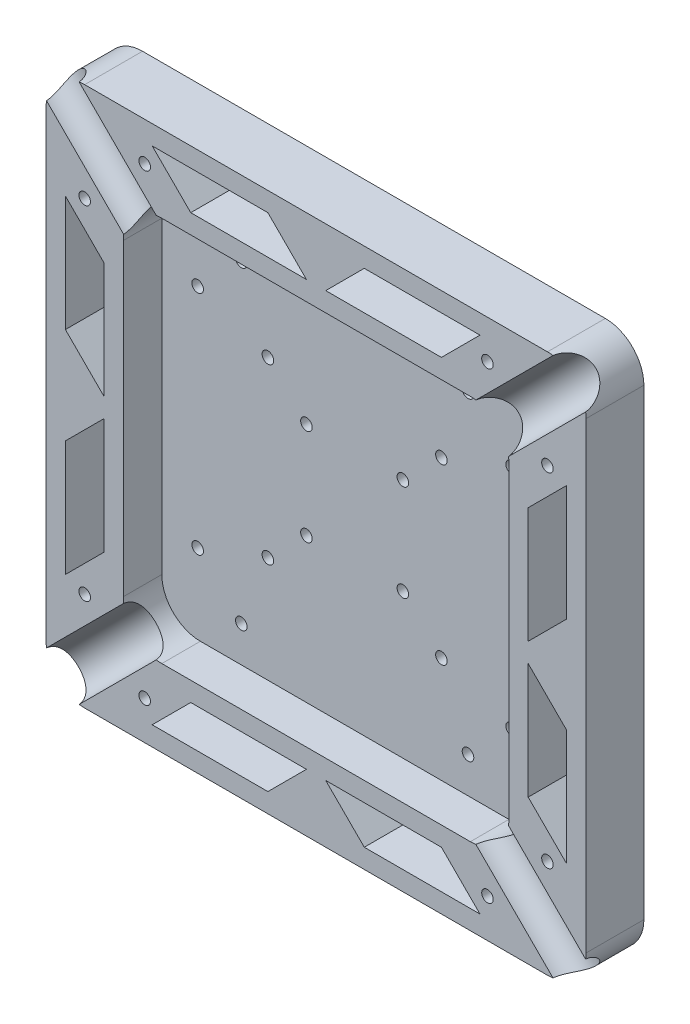
SolidWorks part; units mm, degrees
ref_plane "Plan de face" through (0, 0, 0) normal (0, 0, 1) x (1, 0, 0)
ref_plane "Plan de dessus" through (0, 0, 0) normal (0, 1, 0) x (1, 0, 0)
ref_plane "Plan de droite" through (0, 0, 0) normal (1, 0, 0) x (0, 0, -1)
sketch "Esquisse1" plane through (0, 0, 0) normal (0, 0, 1) x (1, 0, 0)
  line L0 (55, 75.9996) -> (55, -81.4607) construction
  line L1 (-70, 70) -> (70, 70)
  line L2 (-70, 70) -> (-70, -70)
  line L3 (-70, -70) -> (70, -70)
  line L4 (70, 70) -> (70, -70)
  line L9 (65, 75.9996) -> (65, -81.4607) construction
  line L10 (50, 0) -> (70, 0) construction
  line L11 (52.5, 0) -> (65, 12.5) construction
  line L12 (65, 12.5) -> (55, 2.5)
  line L13 (65, -12.5) -> (52.5, 0) construction
  line L14 (65, -12.5) -> (55, -2.5)
  line L15 (65, -12.5) -> (65, -42.5)
  line L16 (65, -42.5) -> (55, -32.5)
  line L17 (55, -32.5) -> (55, -2.5)
  line L18 (65, 12.5) -> (65, 42.5)
  line L19 (65, 42.5) -> (55, 32.5)
  line L20 (55, 32.5) -> (55, 2.5)
  line L21 (12.5, -65) -> (2.5, -55)
  line L22 (-12.5, -65) -> (-2.5, -55)
  line L23 (-12.5, -65) -> (-42.5, -65)
  line L24 (-42.5, -65) -> (-32.5, -55)
  line L25 (-32.5, -55) -> (-2.5, -55)
  line L26 (12.5, -65) -> (42.5, -65)
  line L27 (42.5, -65) -> (32.5, -55)
  line L28 (32.5, -55) -> (2.5, -55)
  line L29 (0, -52.5) -> (12.5, -65) construction
  line L30 (-12.5, -65) -> (0, -52.5) construction
  line L31 (-65, -12.5) -> (-55, -2.5)
  line L32 (-65, 12.5) -> (-55, 2.5)
  line L33 (-65, 12.5) -> (-65, 42.5)
  line L34 (-65, 42.5) -> (-55, 32.5)
  line L35 (-55, 32.5) -> (-55, 2.5)
  line L36 (-65, -12.5) -> (-65, -42.5)
  line L37 (-65, -42.5) -> (-55, -32.5)
  line L38 (-55, -32.5) -> (-55, -2.5)
  line L39 (-52.5, 0) -> (-65, -12.5) construction
  line L40 (-65, 12.5) -> (-52.5, 0) construction
  line L41 (-12.5, 65) -> (-2.5, 55)
  line L42 (12.5, 65) -> (2.5, 55)
  line L43 (12.5, 65) -> (42.5, 65)
  line L44 (42.5, 65) -> (32.5, 55)
  line L45 (32.5, 55) -> (2.5, 55)
  line L46 (-12.5, 65) -> (-42.5, 65)
  line L47 (-42.5, 65) -> (-32.5, 55)
  line L48 (-32.5, 55) -> (-2.5, 55)
  line L49 (0, 52.5) -> (-12.5, 65) construction
  line L50 (12.5, 65) -> (0, 52.5) construction
  dimension "D1" = 140
  dimension "D2" = 140
  dimension "D3" = 70
  dimension "D4" = 70
  dimension "D10" = 5
  dimension "D11" = 2.5
  dimension "D12" = 12.5
  dimension "D13" = 30
  dimension "D14" = 30
  dimension "D15" = 30
  dimension "D16" = 30
  dimension "D17" = 4
extrude "Boss.-Extru.1" add sketch "Esquisse1" along normal blind 15
ref_plane "Plan1" through (0, 0, 0) normal (-0.7071, 0.7071, 0) x (-0.7071, -0.7071, 0)
sketch "Esquisse4" plane through (0, 0, 15) normal (0, 0, 1) x (1, 0, 0)
  line L1 (-50, 50) -> (50, 50)
  line L2 (-50, 50) -> (-50, -50)
  line L3 (-50, -50) -> (50, -50)
  line L4 (50, 50) -> (50, -50)
  dimension "D1" = 100
  dimension "D2" = 100
  dimension "D3" = 50
  dimension "D4" = 50
extrude "Enlèv. mat.-Extru.3" cut sketch "Esquisse4" against normal blind 10
sketch "Esquisse2" plane through (0, 0, 0) normal (-0.7071, 0.7071, 0) x (-0.7071, -0.7071, 0)
  line L0 (99.7696, 15.5) -> (-97.6372, 15.5) construction
  line L1 (-6, 15.5) -> (6, 15.5)
  arc A0 (-6, 15.5) -> (6, 15.5) centre (0, 15.5) ccw
  dimension "D1" = 15.5
extrude "Enlèv. mat.-Extru.1" cut sketch "Esquisse2" against normal blind 100 and the other way blind 100
ref_axis "Axe1" through (0, 0, -62.842) along (0, 0, 1)
pattern_circular "Répétition circulaire1" count 2 every 90 about axis through (0, 0, -62.842) along (0, 0, 1) of "Enlèv. mat.-Extru.1"
fillet "Congé1" radius 10 8 edges at (-70, 70, 4.75) (-70, -70, 4.75) (70, 70, 4.75) (70, -70, 4.75) (50, -50, 7.25) (-50, -50, 7.25) (50, 50, 7.25) (-50, 50, 7.25)
sketch "Esquisse3" plane through (0, 0, 15) normal (0, 0, 1) x (1, 0, 0)
  line L0 (-60, -70) -> (60, -70) construction
  line L1 (-70, 60) -> (-70, -60) construction
  line L2 (45.3482, 45.3482) -> (-45.3482, -45.3482) construction
  circle A0 centre (-60, -44.4437) radius 1.5
  circle A1 centre (-44.4437, -60) radius 1.5
  circle A2 centre (-44.4437, 60) radius 1.5
  circle A3 centre (-60, 44.4437) radius 1.5
  circle A4 centre (60, 44.4437) radius 1.5
  circle A5 centre (44.4437, 60) radius 1.5
  circle A6 centre (44.4437, -60) radius 1.5
  circle A7 centre (60, -44.4437) radius 1.5
  dimension "D1" = 3
  dimension "D2" = 3
  dimension "D3" = 10
  dimension "D4" = 10
  dimension "D5" = 11
  dimension "D6" = 11
  dimension "D7" = 4
extrude "Enlèv. mat.-Extru.2" cut sketch "Esquisse3" against normal blind 15
sketch "Esquisse5" plane through (0, 0, 5) normal (0, 0, 1) x (1, 0, 0)
  line L0 (-70, 60) -> (-70, -60) construction
  line L1 (60, 70) -> (-60, 70) construction
  line L2 (-122.6809, 40) -> (129.5829, 40) construction
  line L3 (-122.6809, -40) -> (137.2895, -40) construction
  line L4 (-40, 87.1964) -> (-40, -85.689) construction
  line L5 (40, 87.1964) -> (40, -83.6339) construction
  line L6 (-60, -70) -> (60, -70) construction
  line L7 (70, -60) -> (70, 60) construction
  line L8 (-40, 40) -> (40, -40) construction
  line L9 (40, 40) -> (-40, -40) construction
  line L10 (27.8934, 42.2071) -> (40.8407, 29.2598) construction
  circle A0 centre (-22.5, 22.5) radius 1.5
  circle A1 centre (22.5, 22.4985) radius 1.5
  circle A2 centre (-22.5, -22.5) radius 1.5
  circle A3 centre (22.5, -22.5015) radius 1.5
  circle A4 centre (-12.5, 12.5) radius 1.5
  circle A5 centre (12.5, 12.5) radius 1.5
  circle A6 centre (12.5, -12.5) radius 1.5
  circle A7 centre (-12.5, -12.5) radius 1.5
  circle A8 centre (29.3934, 40.7071) radius 1.5
  circle A9 centre (40.7071, 29.3934) radius 1.5
  circle A10 centre (40.7071, -29.3934) radius 1.5
  circle A11 centre (29.3934, -40.7071) radius 1.5
  circle A12 centre (-29.3934, -40.7071) radius 1.5
  circle A13 centre (-40.7071, -29.3934) radius 1.5
  circle A14 centre (-40.7071, 29.3934) radius 1.5
  circle A15 centre (-29.3934, 40.7071) radius 1.5
  dimension "D1" = 3
  dimension "D2" = 3
  dimension "D3" = 3
  dimension "D4" = 3
  dimension "D12" = 3
  dimension "D21" = 3
  dimension "D22" = 3
  dimension "D5" = 45
  dimension "D6" = 45
  dimension "D7" = 45
  dimension "D8" = 45
  dimension "D9" = 22.5
  dimension "D10" = 22.5
  dimension "D11" = 57.5
  dimension "D13" = 57.5
  dimension "D15" = 30
  dimension "D16" = 30
  dimension "D17" = 30
  dimension "D18" = 30
  dimension "D19" = 7
  dimension "D20" = 8
  dimension "D23" = 8
  dimension "D14" = 4
  dimension "D24" = 4
extrude "Enlèv. mat.-Extru.4" cut sketch "Esquisse5" against normal blind 5
